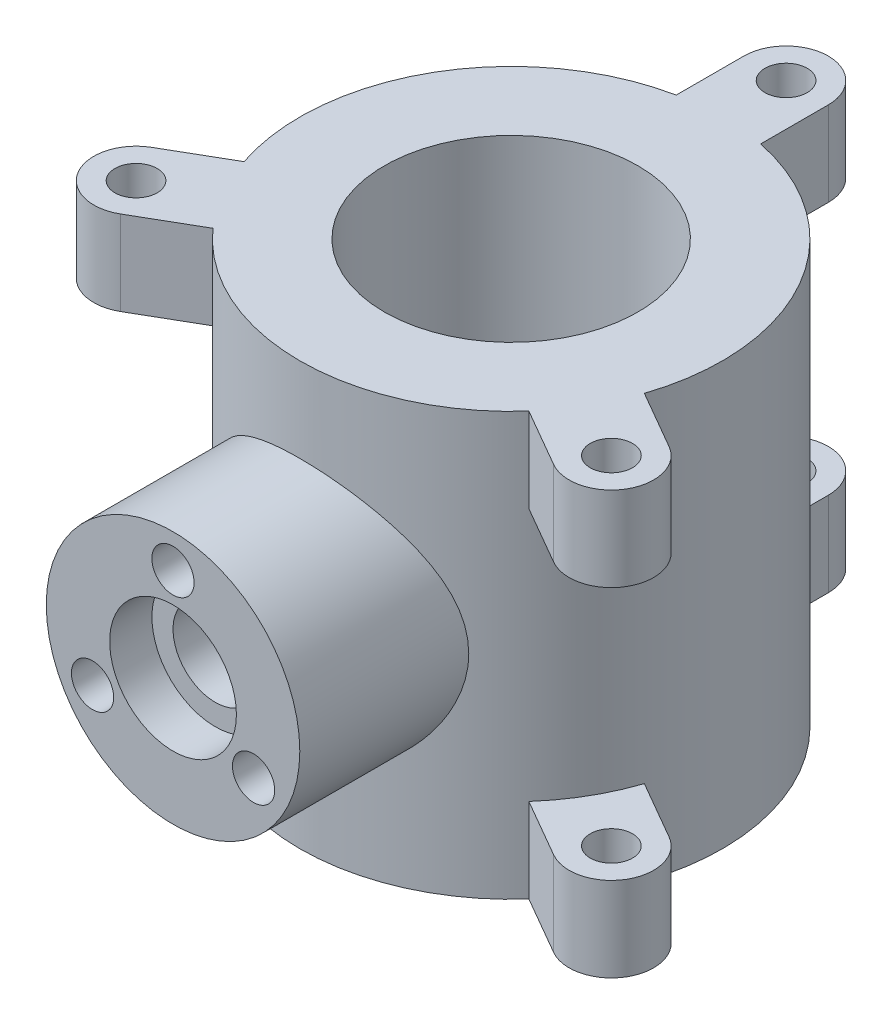
SolidWorks part; units mm, degrees
ref_plane "Front Plane" through (0, 0, 0) normal (0, 0, 1) x (1, 0, 0)
ref_plane "Top Plane" through (0, 0, 0) normal (0, 1, 0) x (1, 0, 0)
ref_plane "Right Plane" through (0, 0, 0) normal (1, 0, 0) x (0, 0, -1)
sketch "Sketch1" plane through (0, 0, 0) normal (0, 1, 0) x (1, 0, 0)
  line L0 (37.3879, -33.1985) -> (51.2644, -41.2101)
  line L2 (10.0568, 48.9782) -> (10.0568, 65.0014)
  line L4 (-9.9432, 49.0014) -> (-9.9432, 65.0014)
  line L5 (47.408, -15.8896) -> (61.2644, -23.8896)
  line L6 (-47.4447, -15.7796) -> (-61.3212, -23.7912)
  line L7 (-37.4648, -33.1117) -> (-51.3212, -41.1117)
  circle A0 centre (0, 0) radius 30
  circle A1 centre (0, 0) radius 50
  arc A2 (10.0568, 65.0014) -> (-9.9432, 65.0014) centre (0.0568, 65.0014) ccw
  circle A3 centre (0.0568, 65.0014) radius 5
  arc A4 (51.2644, -41.2101) -> (61.2644, -23.8896) centre (56.2644, -32.5499) ccw
  circle A5 centre (56.2644, -32.5499) radius 5
  arc A6 (-61.3212, -23.7912) -> (-51.3212, -41.1117) centre (-56.3212, -32.4515) ccw
  circle A7 centre (-56.3212, -32.4515) radius 5
  point P4 (0, 50)
  point P6 (10.0568, 56.9898)
  dimension "D1" = 60
  dimension "D3" = 20
  dimension "D4" = 100
  dimension "D6" = 10
  dimension "D5" = 20
  dimension "D2" = 16
  dimension "D7" = 10
  dimension "D8" = 3
extrude "Boss-Extrude3" add sketch "Sketch1" along normal blind 100 contours A1 A0 region at (-0.0564, 0, 48.5858)
extrude "Boss-Extrude4" add sketch "Sketch1<6>" along normal blind 20 contours L6 A6 L7 A1 A7 | L0 A4 L5 A1 A5 | L2 A2 L4 A1 A3 region at (43.6124, 0, 25.2471) region at (-44.5895, 0, 36.7714) region at (-9.615, 0, -57.0014)
sketch "Sketch1<6>" plane through (0, 0, 0) normal (0, 1, 0) x (1, 0, 0) same geometry as "Sketch1"
ref_plane "Plane1" through (0, 50, 0) normal (0, 1, 0) x (1, 0, 0)
mirror "Mirror3" about plane through (0, 50, 0) normal (0, 1, 0) of "Boss-Extrude4"
ref_plane "Plane2" through (0, 0, 80) normal (0, 0, 1) x (1, 0, 0)
sketch "Sketch2" plane through (0, 0, 80) normal (0, 0, 1) x (1, 0, 0)
  line L0 (0, 0) -> (-0.0385, 100) construction
  line L1 (37.3879, 100) -> (-37.4648, 100) construction
  circle A0 centre (-0.0192, 50) radius 30
  circle A1 centre (-0.0192, 50) radius 15
  circle A2 centre (-0.0192, 50) radius 10
  circle A3 centre (-0.0277, 72) radius 5
  circle A4 centre (19.0376, 39.0073) radius 5
  circle A5 centre (-19.0676, 38.9927) radius 5
  dimension "D1" = 60
  dimension "D2" = 30
  dimension "D3" = 20
  dimension "D4" = 22
  dimension "D5" = 3
extrude "Boss-Extrude6" add sketch "Sketch2" against normal up to next contours L0 A0 A3 A1 A4 | A0 L0 A1 A3 A5 | L0 A1 A2 | A1 L0 A2 | L0 A3 | A3 L0 | A5 | A4 region at (-15.0544, 49.9942, 80) region at (15.0159, 50.0058, 80) region at (-14.6838, 49.9944, 80) region at (0.321, 37.5001, 80) region at (2.0944, 72.0008, 80) region at (-2.1498, 71.9992, 80) region at (19.0376, 39.0073, 80) region at (-19.0676, 38.9927, 80)
extrude "Cut-Extrude1" cut sketch "Sketch2<5>" against normal blind 10 contours L0 A1 A2 | A1 L0 A2 region at (-14.6838, 49.9944, 80) region at (0.321, 37.5001, 80)
sketch "Sketch2<5>" plane through (0, 0, 80) normal (0, 0, 1) x (1, 0, 0) same geometry as "Sketch2"
extrude "Cut-Extrude2" cut sketch "Sketch2<6>" against normal blind 10 contours L0 A3 | A3 L0 | A4 | A5 region at (2.0944, 72.0008, 80) region at (-2.1498, 71.9992, 80) region at (19.0376, 39.0073, 80) region at (-19.0676, 38.9927, 80)
sketch "Sketch2<6>" plane through (0, 0, 80) normal (0, 0, 1) x (1, 0, 0) same geometry as "Sketch2"
extrude "Cut-Extrude3" cut sketch "Sketch2<7>" against normal up to next contours A2 L0 | L0 A2 region at (-4.2634, 49.9984, 80) region at (4.2249, 50.0016, 80)
sketch "Sketch2<7>" plane through (0, 0, 80) normal (0, 0, 1) x (1, 0, 0) same geometry as "Sketch2"
